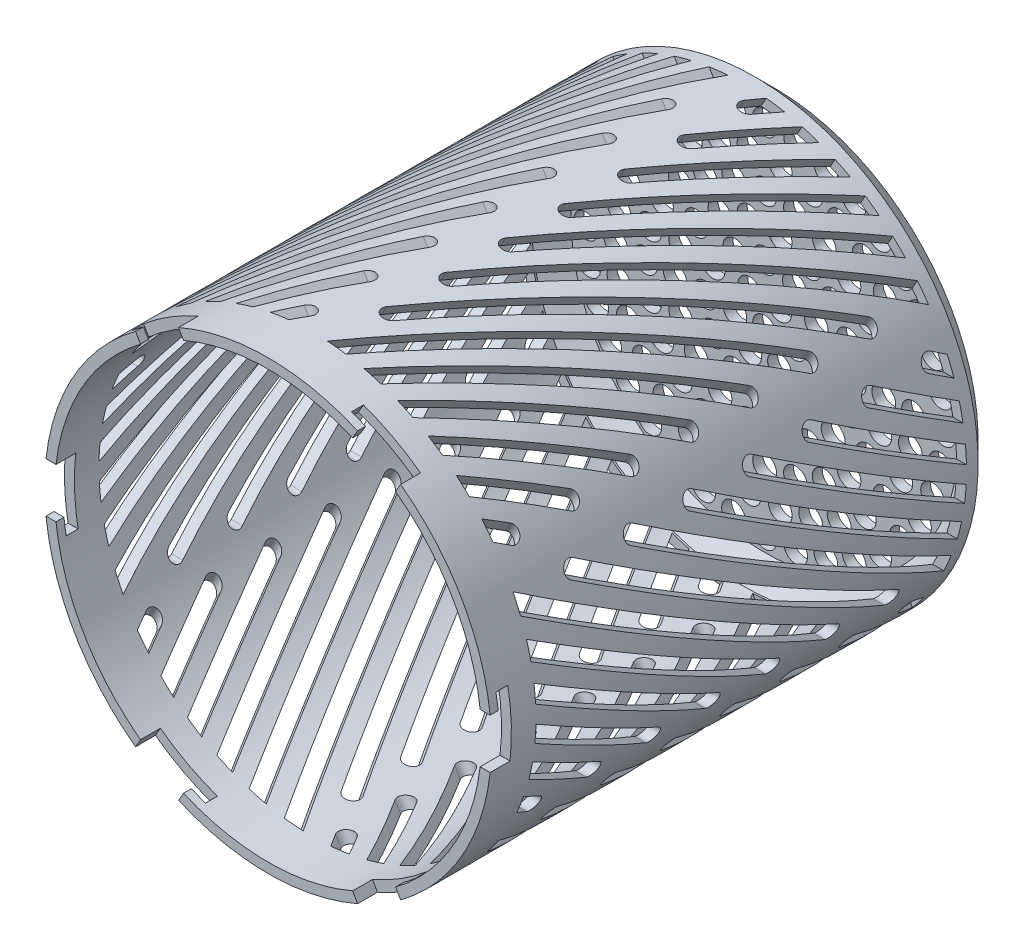
SolidWorks part; units mm, degrees
ref_plane "前视基准面" through (0, 0, 0) normal (0, 0, 1) x (1, 0, 0)
ref_plane "上视基准面" through (0, 0, 0) normal (0, 1, 0) x (1, 0, 0)
ref_plane "右视基准面" through (0, 0, 0) normal (1, 0, 0) x (0, 0, -1)
sketch "草图1" plane through (0, 0, 0) normal (0, 0, 1) x (1, 0, 0)
  circle A0 centre (0, 0) radius 22.5
  circle A1 centre (0, 0) radius 21.5
  dimension "D1" = 45
  dimension "D2" = 43
extrude "凸台-拉伸1" add sketch "草图1" along normal blind 50
sketch "草图2" plane through (0, 0, 0) normal (0, 0, -1) x (-1, 0, 0)
  circle A0 centre (0, 0) radius 22.5
extrude "凸台-拉伸2" add sketch "草图2" along normal blind 1
chamfer "倒角1" distance 2 angle 45 2 edges at (-22.5, 0, -1) (21.5, 0, 0)
sketch "草图3" plane through (0, 0, -1) normal (0, 0, -1) x (-1, 0, 0)
  circle A0 centre (0, 0) radius 1.2
  circle A1 centre (0, 0) radius 3 construction
  circle A3 centre (0, 0) radius 6 construction
  circle A4 centre (0, 0) radius 9 construction
  circle A5 centre (0, 0) radius 12 construction
  circle A6 centre (0, 0) radius 15 construction
  circle A7 centre (0, 0) radius 18 construction
  circle A8 centre (3, 0) radius 1.2
  circle A9 centre (6, 0) radius 1.2
  circle A10 centre (9, 0) radius 1.2
  circle A11 centre (12, 0) radius 1.2
  circle A12 centre (15, 0) radius 1.2
  circle A13 centre (18, 0) radius 1.2
  circle A14 centre (1.5, -2.5981) radius 1.2
  circle A15 centre (-1.5, -2.5981) radius 1.2
  circle A16 centre (-3, 0) radius 1.2
  circle A17 centre (-1.5, 2.5981) radius 1.2
  circle A18 centre (1.5, 2.5981) radius 1.2
  circle A19 centre (5.1962, -3) radius 1.2
  circle A20 centre (3, -5.1962) radius 1.2
  circle A21 centre (0, -6) radius 1.2
  circle A22 centre (-3, -5.1962) radius 1.2
  circle A23 centre (-5.1962, -3) radius 1.2
  circle A24 centre (-6, 0) radius 1.2
  circle A25 centre (-5.1962, 3) radius 1.2
  circle A26 centre (-3, 5.1962) radius 1.2
  circle A27 centre (0, 6) radius 1.2
  circle A28 centre (3, 5.1962) radius 1.2
  circle A29 centre (5.1962, 3) radius 1.2
  circle A30 centre (8.4572, -3.0782) radius 1.2
  circle A31 centre (6.8944, -5.7851) radius 1.2
  circle A32 centre (4.5, -7.7942) radius 1.2
  circle A33 centre (1.5628, -8.8633) radius 1.2
  circle A34 centre (-1.5628, -8.8633) radius 1.2
  circle A35 centre (-4.5, -7.7942) radius 1.2
  circle A36 centre (-6.8944, -5.7851) radius 1.2
  circle A37 centre (-8.4572, -3.0782) radius 1.2
  circle A38 centre (-9, 0) radius 1.2
  circle A39 centre (-8.4572, 3.0782) radius 1.2
  circle A40 centre (-6.8944, 5.7851) radius 1.2
  circle A41 centre (-4.5, 7.7942) radius 1.2
  circle A42 centre (-1.5628, 8.8633) radius 1.2
  circle A43 centre (1.5628, 8.8633) radius 1.2
  circle A44 centre (4.5, 7.7942) radius 1.2
  circle A45 centre (6.8944, 5.7851) radius 1.2
  circle A46 centre (8.4572, 3.0782) radius 1.2
  circle A47 centre (11.5911, -3.1058) radius 1.2
  circle A48 centre (10.3923, -6) radius 1.2
  circle A49 centre (8.4853, -8.4853) radius 1.2
  circle A50 centre (6, -10.3923) radius 1.2
  circle A51 centre (3.1058, -11.5911) radius 1.2
  circle A52 centre (0, -12) radius 1.2
  circle A53 centre (-3.1058, -11.5911) radius 1.2
  circle A54 centre (-6, -10.3923) radius 1.2
  circle A55 centre (-8.4853, -8.4853) radius 1.2
  circle A56 centre (-10.3923, -6) radius 1.2
  circle A57 centre (-11.5911, -3.1058) radius 1.2
  circle A58 centre (-12, 0) radius 1.2
  circle A59 centre (-11.5911, 3.1058) radius 1.2
  circle A60 centre (-10.3923, 6) radius 1.2
  circle A61 centre (-8.4853, 8.4853) radius 1.2
  circle A62 centre (-6, 10.3923) radius 1.2
  circle A63 centre (-3.1058, 11.5911) radius 1.2
  circle A64 centre (0, 12) radius 1.2
  circle A65 centre (3.1058, 11.5911) radius 1.2
  circle A66 centre (6, 10.3923) radius 1.2
  circle A67 centre (8.4853, 8.4853) radius 1.2
  circle A68 centre (10.3923, 6) radius 1.2
  circle A69 centre (11.5911, 3.1058) radius 1.2
  circle A70 centre (14.6722, -3.1187) radius 1.2
  circle A71 centre (13.7032, -6.101) radius 1.2
  circle A72 centre (12.1353, -8.8168) radius 1.2
  circle A73 centre (10.037, -11.1472) radius 1.2
  circle A74 centre (7.5, -12.9904) radius 1.2
  circle A75 centre (4.6353, -14.2658) radius 1.2
  circle A76 centre (1.5679, -14.9178) radius 1.2
  circle A77 centre (-1.5679, -14.9178) radius 1.2
  circle A78 centre (-4.6353, -14.2658) radius 1.2
  circle A79 centre (-7.5, -12.9904) radius 1.2
  circle A80 centre (-10.037, -11.1472) radius 1.2
  circle A81 centre (-12.1353, -8.8168) radius 1.2
  circle A82 centre (-13.7032, -6.101) radius 1.2
  circle A83 centre (-14.6722, -3.1187) radius 1.2
  circle A84 centre (-15, 0) radius 1.2
  circle A85 centre (-14.6722, 3.1187) radius 1.2
  circle A86 centre (-13.7032, 6.101) radius 1.2
  circle A87 centre (-12.1353, 8.8168) radius 1.2
  circle A88 centre (-10.037, 11.1472) radius 1.2
  circle A89 centre (-7.5, 12.9904) radius 1.2
  circle A90 centre (-4.6353, 14.2658) radius 1.2
  circle A91 centre (-1.5679, 14.9178) radius 1.2
  circle A92 centre (1.5679, 14.9178) radius 1.2
  circle A93 centre (4.6353, 14.2658) radius 1.2
  circle A94 centre (7.5, 12.9904) radius 1.2
  circle A95 centre (10.037, 11.1472) radius 1.2
  circle A96 centre (12.1353, 8.8168) radius 1.2
  circle A97 centre (13.7032, 6.101) radius 1.2
  circle A98 centre (14.6722, 3.1187) radius 1.2
  circle A99 centre (17.7265, -3.1257) radius 1.2
  circle A100 centre (16.9145, -6.1564) radius 1.2
  circle A101 centre (15.5885, -9) radius 1.2
  circle A102 centre (13.7888, -11.5702) radius 1.2
  circle A103 centre (11.5702, -13.7888) radius 1.2
  circle A104 centre (9, -15.5885) radius 1.2
  circle A105 centre (6.1564, -16.9145) radius 1.2
  circle A106 centre (3.1257, -17.7265) radius 1.2
  circle A107 centre (0, -18) radius 1.2
  circle A108 centre (-3.1257, -17.7265) radius 1.2
  circle A109 centre (-6.1564, -16.9145) radius 1.2
  circle A110 centre (-9, -15.5885) radius 1.2
  circle A111 centre (-11.5702, -13.7888) radius 1.2
  circle A112 centre (-13.7888, -11.5702) radius 1.2
  circle A113 centre (-15.5885, -9) radius 1.2
  circle A114 centre (-16.9145, -6.1564) radius 1.2
  circle A115 centre (-17.7265, -3.1257) radius 1.2
  circle A116 centre (-18, 0) radius 1.2
  circle A117 centre (-17.7265, 3.1257) radius 1.2
  circle A118 centre (-16.9145, 6.1564) radius 1.2
  circle A119 centre (-15.5885, 9) radius 1.2
  circle A120 centre (-13.7888, 11.5702) radius 1.2
  circle A121 centre (-11.5702, 13.7888) radius 1.2
  circle A122 centre (-9, 15.5885) radius 1.2
  circle A123 centre (-6.1564, 16.9145) radius 1.2
  circle A124 centre (-3.1257, 17.7265) radius 1.2
  circle A125 centre (0, 18) radius 1.2
  circle A126 centre (3.1257, 17.7265) radius 1.2
  circle A127 centre (6.1564, 16.9145) radius 1.2
  circle A128 centre (9, 15.5885) radius 1.2
  circle A129 centre (11.5702, 13.7888) radius 1.2
  circle A130 centre (13.7888, 11.5702) radius 1.2
  circle A131 centre (15.5885, 9) radius 1.2
  circle A132 centre (16.9145, 6.1564) radius 1.2
  circle A133 centre (17.7265, 3.1257) radius 1.2
  point P33 (0, 0)
  point P56 (0, 0)
  point P91 (0, 0)
  point P138 (0, 0)
  point P198 (0, 0)
  point P268 (0, 0)
  dimension "D1" = 2.4
  dimension "D2" = 6
  dimension "D3" = 7
  dimension "D4" = 12
  dimension "D5" = 18
  dimension "D6" = 24
  dimension "D7" = 30
  dimension "D8" = 36
  dimension "D9" = 6
  dimension "D10" = 12
  dimension "D11" = 18
  dimension "D12" = 24
  dimension "D13" = 30
  dimension "D14" = 36
extrude "切除-拉伸1" cut sketch "草图3" against normal blind 12
sketch "草图4" plane through (0, 0, 50) normal (0, 0, 1) x (1, 0, 0)
  line L1 (-27.2924, -2.5) -> (27.2924, -2.5)
  line L2 (-27.2924, -2.5) -> (-27.2924, 2.5)
  line L3 (-27.2924, 2.5) -> (27.2924, 2.5)
  line L4 (27.2924, -2.5) -> (27.2924, 2.5)
  line L5 (-27.2924, -2.5) -> (27.2924, 2.5) construction
  line L6 (-27.2924, 2.5) -> (27.2924, -2.5) construction
  point P0 (0, 0)
  dimension "D1" = 5
extrude "切除-拉伸2" cut sketch "草图4" against normal blind 2
ref_plane "基准面4" through (-22.5, 0, 48) normal (-1, 0, 0) x (0, 0, 1)
sketch "草图5" plane through (-22.5, 0, 48) normal (-1, 0, 0) x (0, 0, 1)
  line L0 (-2.4727, 7.3861) -> (-4.576, 8.6005)
  line L7 (-2.4727, 5.6541) -> (-9.826, 9.8995)
  line L57 (-45.826, 9.8995) -> (-45.826, 8.1675)
  line L58 (-2.4727, 9.1182) -> (-3.826, 9.8995)
  line L59 (-2.4727, 3.922) -> (-10.576, 8.6005)
  line L60 (-2.4727, 2.19) -> (-15.826, 9.8995)
  line L61 (-2.4727, 0.4579) -> (-16.576, 8.6005)
  line L62 (-2.4727, -1.2741) -> (-21.826, 9.8995)
  line L63 (-2.4727, -3.0062) -> (-22.576, 8.6005)
  line L64 (-2.4727, -4.7382) -> (-27.826, 9.8995)
  line L65 (-2.4727, -6.4703) -> (-28.576, 8.6005)
  line L66 (-2.4727, -8.2023) -> (-33.826, 9.8995)
  line L67 (-2.4727, -9.9344) -> (-34.576, 8.6005)
  line L68 (-7.7227, -8.6353) -> (-39.826, 9.8995)
  line L69 (-8.4727, -9.9344) -> (-40.576, 8.6005)
  line L70 (-13.7227, -8.6353) -> (-45.826, 9.8995)
  line L71 (-14.4727, -9.9344) -> (-45.826, 8.1675)
  line L72 (-19.7227, -8.6353) -> (-45.826, 6.4354)
  line L73 (-20.4727, -9.9344) -> (-45.826, 4.7034)
  line L74 (-25.7227, -8.6353) -> (-45.826, 2.9713)
  line L75 (-26.4727, -9.9344) -> (-45.826, 1.2393)
  line L76 (-31.7227, -8.6353) -> (-45.826, -0.4928)
  line L77 (-32.4727, -9.9344) -> (-45.826, -2.2248)
  line L78 (-37.7227, -8.6353) -> (-45.826, -3.9569)
  line L79 (-38.4727, -9.9344) -> (-45.826, -5.6889)
  line L80 (-43.7227, -8.6353) -> (-45.826, -7.421)
  line L81 (-44.4727, -9.9344) -> (-45.826, -9.153)
  line L106 (-2.4727, 3.922) -> (-2.4727, 5.6541)
  line L108 (-2.4727, 7.3861) -> (-2.4727, 9.1182)
  line L116 (-45.826, 6.4354) -> (-45.826, 4.7034)
  line L117 (-45.826, 2.9713) -> (-45.826, 1.2393)
  line L118 (-45.826, -0.4928) -> (-45.826, -2.2248)
  line L119 (-45.826, -3.9569) -> (-45.826, -5.6889)
  line L120 (-45.826, -7.421) -> (-45.826, -9.153)
  line L121 (-2.4727, -9.9344) -> (-2.4727, -8.2023)
  line L122 (-0.0228, -10.0348) -> (-0.0201, -10.0348) construction
  line L123 (-2.4727, 0.4579) -> (-2.4727, 2.19)
  line L124 (-2.4727, -3.0062) -> (-2.4727, -1.2741)
  line L125 (-2.4727, -6.4703) -> (-2.4727, -4.7382)
  line L126 (-0.0228, -10.0348) -> (-0.0201, -10.0348) construction
  arc A0 (-3.826, 9.8995) -> (-4.576, 8.6005) centre (-4.201, 9.25) ccw
  arc A2 (-9.826, 9.8995) -> (-10.576, 8.6005) centre (-10.201, 9.25) ccw
  arc A5 (-15.826, 9.8995) -> (-16.576, 8.6005) centre (-16.201, 9.25) ccw
  arc A6 (-21.826, 9.8995) -> (-22.576, 8.6005) centre (-22.201, 9.25) ccw
  arc A7 (-27.826, 9.8995) -> (-28.576, 8.6005) centre (-28.201, 9.25) ccw
  arc A8 (-33.826, 9.8995) -> (-34.576, 8.6005) centre (-34.201, 9.25) ccw
  arc A9 (-39.826, 9.8995) -> (-40.576, 8.6005) centre (-40.201, 9.25) ccw
  arc A18 (-8.4727, -9.9344) -> (-7.7227, -8.6353) centre (-8.0977, -9.2848) ccw
  arc A19 (-14.4727, -9.9344) -> (-13.7227, -8.6353) centre (-14.0977, -9.2848) ccw
  arc A20 (-20.4727, -9.9344) -> (-19.7227, -8.6353) centre (-20.0977, -9.2848) ccw
  arc A21 (-26.4727, -9.9344) -> (-25.7227, -8.6353) centre (-26.0977, -9.2848) ccw
  arc A22 (-32.4727, -9.9344) -> (-31.7227, -8.6353) centre (-32.0977, -9.2848) ccw
  arc A23 (-38.4727, -9.9344) -> (-37.7227, -8.6353) centre (-38.0977, -9.2848) ccw
  arc A24 (-44.4727, -9.9344) -> (-43.7227, -8.6353) centre (-44.0977, -9.2848) ccw
  arc A25 (-46.8505, 9.625) -> (-46.576, 8.6005) centre (-46.201, 9.25) ccw
  point P0 (-23.5, 0)
  point P2 (0, 0)
  dimension "D1" = 1.5
  dimension "D5" = 1.5
  dimension "D4" = 26
  dimension "D7" = 7
extrude "切除-拉伸3" cut sketch "草图5" against normal blind 5
pattern_circular "阵列(圆周)1" count 6 over 360 about axis through (0, 0, 0) along (0, 0, 1) of "切除-拉伸3"
sketch "草图6" plane through (0, 0, 48) normal (0, 0, 1) x (1, 0, 0)
  line L1 (18.8725, 1) -> (23.8358, 1)
  line L2 (18.8725, 1) -> (18.8725, 4)
  line L3 (18.8725, 4) -> (23.8358, 4)
  line L4 (23.8358, 1) -> (23.8358, 4)
  line L5 (18.8725, 1) -> (23.8358, 4) construction
  line L6 (18.8725, 4) -> (23.8358, 1) construction
  point P0 (21.3542, 2.5)
  dimension "D1" = 3
extrude "切除-拉伸4" cut sketch "草图6" along normal blind 1.2
pattern_circular "阵列(圆周)2" count 6 over 360 about axis through (0, 0, 0) along (0, 0, 1) of "切除-拉伸2", "切除-拉伸4"
